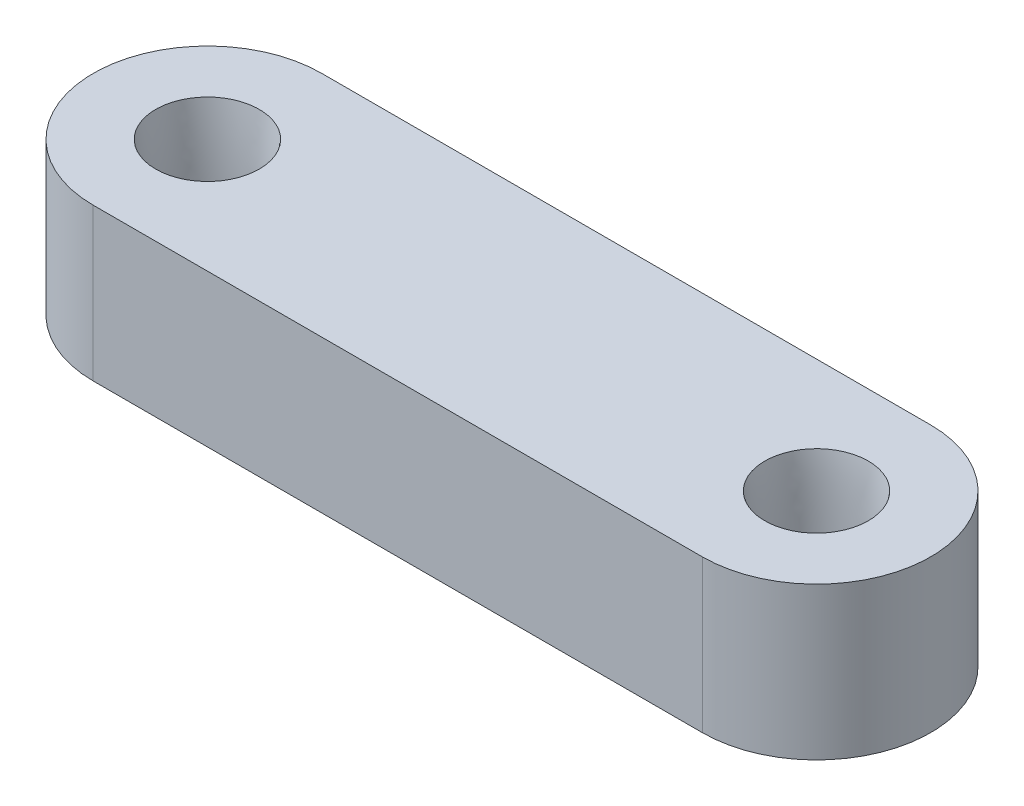
SolidWorks part; units mm, degrees
ref_plane "Front Plane" through (0, 0, 0) normal (0, 0, 1) x (1, 0, 0)
ref_plane "Top Plane" through (0, 0, 0) normal (0, 1, 0) x (1, 0, 0)
ref_plane "Right Plane" through (0, 0, 0) normal (1, 0, 0) x (0, 0, -1)
sketch "Sketch1" plane through (0, 0, 0) normal (0, 1, 0) x (1, 0, 0)
  line L0 (0, 0) -> (20, 0) construction
  line L1 (0, 3.75) -> (20, 3.75)
  line L2 (0, -3.75) -> (20, -3.75)
  arc A0 (0, 3.75) -> (0, -3.75) centre (0, 0) ccw
  arc A2 (20, -3.75) -> (20, 3.75) centre (20, 0) ccw
  arc A3 (16.25, 0) -> (20, -3.75) centre (20, 0) ccw construction
  arc A4 (20, 3.75) -> (16.25, 0) centre (20, 0) ccw construction
  arc A5 (3.75, 0) -> (0, 3.75) centre (0, 0) ccw construction
  arc A6 (0, -3.75) -> (3.75, 0) centre (0, 0) ccw construction
  dimension "D1" = 7.5
  dimension "D2" = 20
extrude "Boss-Extrude1" add sketch "Sketch1" along normal blind 5
sketch "Sketch2" plane through (0, 5, 0) normal (0, 1, 0) x (1, 0, 0)
  circle A0 centre (0, 0) radius 1.7
  circle A1 centre (20, 0) radius 1.7
  dimension "D1" = 3.4
sketch "Sketch3" plane through (0, 0, 0) normal (0, -1, 0) x (1, 0, 0)
  circle A0 centre (0, 0) radius 1.7
  circle A1 centre (20, 0) radius 1.7
  dimension "D1" = 3.4
ref_plane "Plane1" through (0, 2.5, 0) normal (0, -1, 0) x (-1, 0, 0)
sketch "Sketch4" plane through (0, 2.5, 0) normal (0, -1, 0) x (-1, 0, 0)
  circle A0 centre (-20, 0) radius 1.6
  circle A1 centre (0, 0) radius 1.6
  dimension "D1" = 3.2
loft "Cut-Loft2" cut section "Sketch3" section "Sketch4" section "Sketch2" connector at (0.5929, 0, 1.5933) connector at (0.6188, 2.5, 1.4755) connector at (1.1402, 5, 1.261)
loft "Cut-Loft3" cut section "Sketch2<11>" section "Sketch4<4>" section "Sketch3<11>" start constraint default end constraint default connector at (18.9597, 5, 1.3446) connector at (18.6966, 2.5, 0.928) connector at (18.9016, 0, 1.2975)
sketch "Sketch2<11>" plane through (0, 5, 0) normal (0, 1, 0) x (1, 0, 0) same geometry as "Sketch2"
sketch "Sketch4<4>" plane through (0, 2.5, 0) normal (0, -1, 0) x (-1, 0, 0) same geometry as "Sketch4"
sketch "Sketch3<11>" plane through (0, 0, 0) normal (0, -1, 0) x (1, 0, 0) same geometry as "Sketch3"
